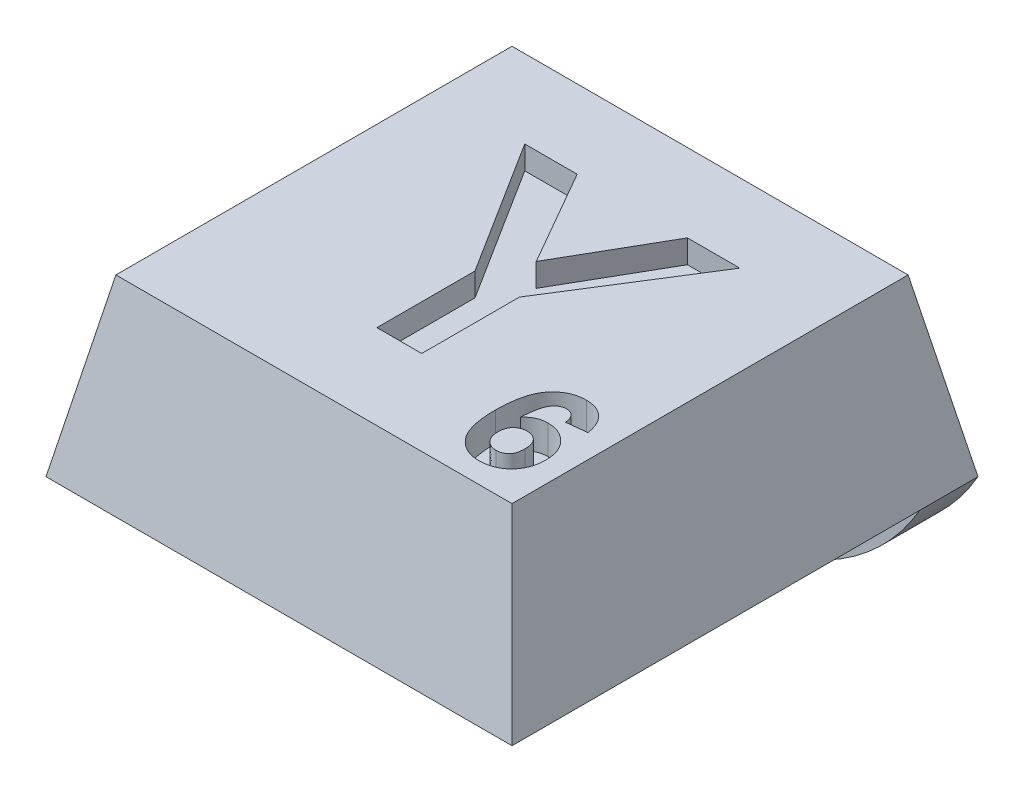
SolidWorks part; units mm, degrees
ref_plane "Front Plane" through (0, 0, 0) normal (0, 0, 1) x (1, 0, 0)
ref_plane "Top Plane" through (0, 0, 0) normal (0, 1, 0) x (1, 0, 0)
ref_plane "Right Plane" through (0, 0, 0) normal (1, 0, 0) x (0, 0, -1)
sketch "Sketch1" plane through (0, 0, 0) normal (0, 1, 0) x (1, 0, 0)
  line L1 (0, 0) -> (8, 0)
  line L2 (0, 0) -> (0, 8)
  line L3 (0, 8) -> (8, 8)
  line L4 (8, 0) -> (8, 8)
  dimension "D1" = 8
  dimension "D2" = 8
extrude "Boss-Extrude1" add sketch "Sketch1" along normal blind 3
sketch "Sketch2" plane through (0, 0, 0) normal (0, 0, 1) x (1, 0, 0)
  line L0 (0, 0) -> (0.6, 3)
  line L1 (0, 3) -> (8, 3) construction
  line L2 (0.6, 3) -> (0, 3)
  line L3 (0, 3) -> (0, 0)
  line L4 (8, 0) -> (7.4, 3)
  line L5 (7.4, 3) -> (8, 3)
  line L6 (8, 3) -> (8, 0)
  dimension "D1" = 0.6
  dimension "D2" = 0.6
extrude "Cut-Extrude1" cut sketch "Sketch2" against normal through all both and the other way through all
sketch "Sketch3" plane through (0, 0, 0) normal (1, 0, 0) x (0, 0, -1)
  line L0 (0, 0) -> (0.6, 3)
  line L1 (8, 3) -> (0, 3) construction
  line L2 (0.6, 3) -> (0, 3)
  line L3 (0, 3) -> (0, 0)
  line L4 (8, 3) -> (7.4, 3)
  line L5 (7.4, 3) -> (8, 0)
  line L6 (8, 3) -> (8, 0)
  dimension "D1" = 0.6
  dimension "D2" = 0.6
extrude "Cut-Extrude2" cut sketch "Sketch3" along normal blind 11
sketch "Sketch4" plane through (0, 0, 0) normal (0, -1, 0) x (1, 0, 0)
  line L0 (8, 0) -> (8, -8) construction
  line L3 (0, 0) -> (8, 0) construction
  circle A0 centre (4, -3.75) radius 1.75
  dimension "D1" = 3.5
  dimension "D2" = 4
  dimension "D3" = 3.75
extrude "Cut-Extrude3" cut sketch "Sketch4" against normal blind 0.4
sketch "Sketch5" plane through (0, 0, 0) normal (0, -1, 0) x (1, 0, 0)
  line L0 (8, 0) -> (8, -8) construction
  line L1 (0, -8) -> (8, -8)
  line L2 (0, -8) -> (0, -7)
  line L3 (0, -7) -> (8, -7)
  line L4 (8, -8) -> (8, -7)
  dimension "D1" = 1
extrude "Boss-Extrude2" add sketch "Sketch5" along normal blind 2
fillet "Fillet1" radius 4 2 edges at (8, -2, -7.5) (0, -2, -7.5)
sketch "Sketch6" plane through (0, 3, 0) normal (0, 1, 0) x (1, 0, 0)
  text T0 "Y" font "Arial" height 4
extrude "Cut-Extrude4" cut sketch "Sketch6" against normal blind 0.4
sketch "Sketch7" plane through (0, 3, 0) normal (0, 1, 0) x (1, 0, 0)
  text T0 "6" font "Arial" height 1.8
extrude "Cut-Extrude5" cut sketch "Sketch7" against normal blind 0.5
